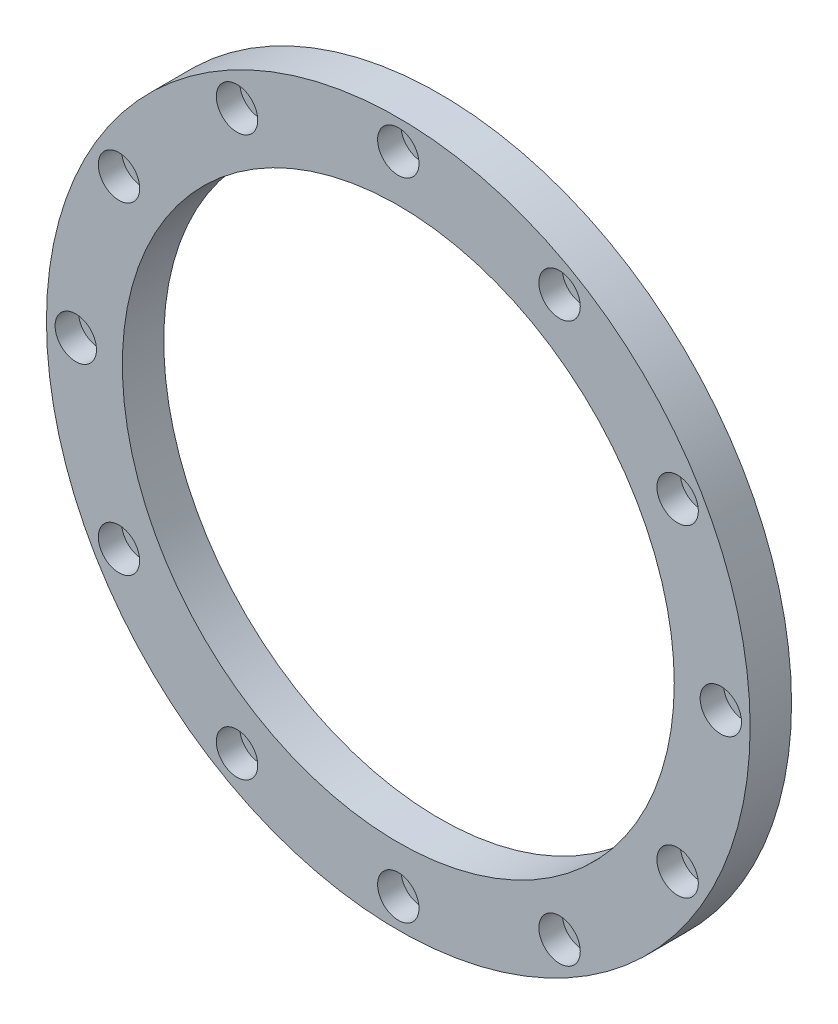
SolidWorks part; units mm, degrees
ref_plane "前视基准面" through (0, 0, 0) normal (0, 0, 1) x (1, 0, 0)
ref_plane "上视基准面" through (0, 0, 0) normal (0, 1, 0) x (1, 0, 0)
ref_plane "右视基准面" through (0, 0, 0) normal (1, 0, 0) x (0, 0, -1)
sketch "草图1" plane through (0, 0, 0) normal (0, 0, 1) x (1, 0, 0)
  circle A0 centre (0, 0) radius 51
  dimension "D1" = 102
extrude "凸台-拉伸1" add sketch "草图1" along normal blind 6
hole_wizard "打孔尺寸(%根据)内六角圆柱头螺钉的类型1" positions "草图3" profile "草图2" counterbore size "M3" standard "GB" end condition through all
sketch "草图3" plane through (0, 0, 6) normal (0, 0, 1) x (1, 0, 0)
  line L0 (0, 0) -> (0, 54.0965) construction
  circle A0 centre (0, 0) radius 46.75 construction
  point P0 (0, 46.75)
  dimension "D1" = 93.5
sketch "草图2" plane through (0, 46.75, 6) normal (1, 0, 0) x (0, -1, 0)
  line L0 (0, 0) -> (0, 6)
  line L1 (0, 6) -> (1.7, 6)
  line L3 (1.7, 6) -> (1.7, 3.4)
  line L4 (1.7, 3.4) -> (3, 3.4)
  line L5 (3, 3.4) -> (3, 0)
  line L7 (3, 0) -> (0, 0)
  line L11 (0, -6.35) -> (0, 107.95) construction
  dimension "通孔孔直径" = 3.4
  dimension "通孔孔深度" = 6
  dimension "柱形沉头孔直径" = 6
  dimension "柱形沉头孔深度" = 3.4
sketch "草图4" plane through (0, 0, 6) normal (0, 0, 1) x (1, 0, 0)
  circle A0 centre (0, 0) radius 40
  dimension "D1" = 80
extrude "切除-拉伸1" cut sketch "草图4" against normal through all
ref_axis "基准轴1" through (0, 0, 0) along (0, 0, 1)
pattern_circular "阵列(圆周)1" count 12 over 360 about axis through (0, 0, 0) along (0, 0, 1) of "打孔尺寸(%根据)内六角圆柱头螺钉的类型1"
